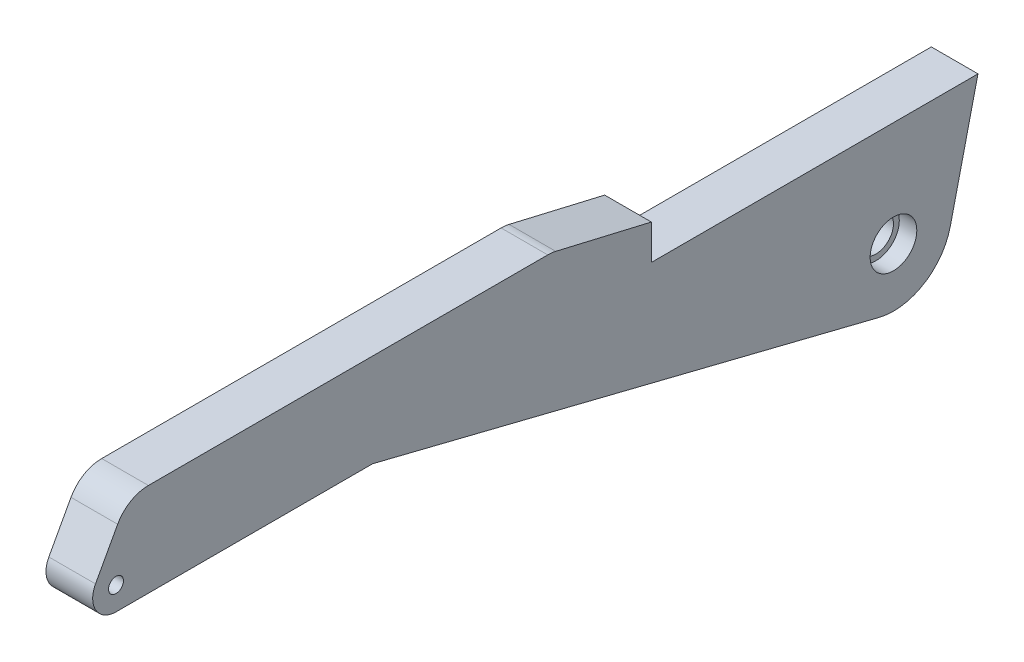
SolidWorks part; units mm, degrees
ref_plane "Front Plane" through (0, 0, 0) normal (0, 0, 1) x (1, 0, 0)
ref_plane "Top Plane" through (0, 0, 0) normal (0, 1, 0) x (1, 0, 0)
ref_plane "Right Plane" through (0, 0, 0) normal (1, 0, 0) x (0, 0, -1)
sketch "Sketch1" plane through (0, 0, 0) normal (1, 0, 0) x (0, 0, -1)
  line L0 (-5.5746, 3.0408) -> (3.158, 19.05)
  line L1 (3.158, 19.05) -> (118.6087, 19.05)
  line L2 (118.6087, 19.05) -> (145.6969, 12.7)
  line L3 (145.6969, 12.7) -> (145.6969, 3.175)
  line L4 (145.6969, 3.175) -> (234.5969, 3.175)
  line L5 (234.5969, 3.175) -> (227.049, -29.0232)
  line L6 (0, -6.35) -> (69.85, -6.35)
  line L7 (69.85, -6.35) -> (207.7451, -40.8016)
  line L8 (-5.5746, 3.0408) -> (7.9306, 27.7995) construction
  line L9 (207.7451, -40.8016) -> (69.85, -6.35) construction
  line L10 (234.5969, 3.175) -> (227.049, -29.0232) construction
  line L11 (145.6969, 3.175) -> (234.5969, 3.175) construction
  line L12 (69.85, 30.48) -> (145.6969, 12.7) construction
  line L13 (145.6969, 12.7) -> (145.6969, 3.175) construction
  circle A0 centre (0, 0) radius 2.032
  arc A1 (-5.5746, 3.0408) -> (0, -6.35) centre (0, 0) ccw
  arc A2 (227.049, -29.0232) -> (207.7451, -40.8016) centre (211.593, -25.4) cw
  arc A3 (-5.5746, 3.0408) -> (0, -6.35) centre (0, 0) ccw construction
  arc A4 (207.7451, -40.8016) -> (227.049, -29.0232) centre (211.593, -25.4) ccw construction
  point P13 (100.1802, -1.0836)
  point P20 (64.6766, -6.35)
  point P23 (203.7007, -11.0627)
  point P29 (238.9352, 1.6601)
  point P32 (148.0299, 3.8936)
  dimension "D1" = 4.064
  dimension "D2" = 25.4
extrude "Boss-Extrude1" add sketch "Sketch1" along normal blind 12.7
fillet "Fillet1" radius 9.525 2 edges at (6.35, 19.05, -118.6087) (6.35, 19.05, -3.158)
sketch "Sketch2" plane through (0, 0, 0) normal (-1, 0, 0) x (0, 0, 1)
  circle A0 centre (-211.593, -25.4) radius 4.7625
  arc A1 (-227.049, -29.0232) -> (-207.7451, -40.8016) centre (-211.593, -25.4) ccw construction
  dimension "D1" = 9.525
extrude "Cut-Extrude1" cut sketch "Sketch2" against normal through all
sketch "Sketch4" plane through (12.7, 0, 0) normal (1, 0, 0) x (0, 0, -1)
  circle A0 centre (211.593, -25.4) radius 6.35
  dimension "D1" = 12.7
extrude "Cut-Extrude2" cut sketch "Sketch4" against normal blind 4.7625
